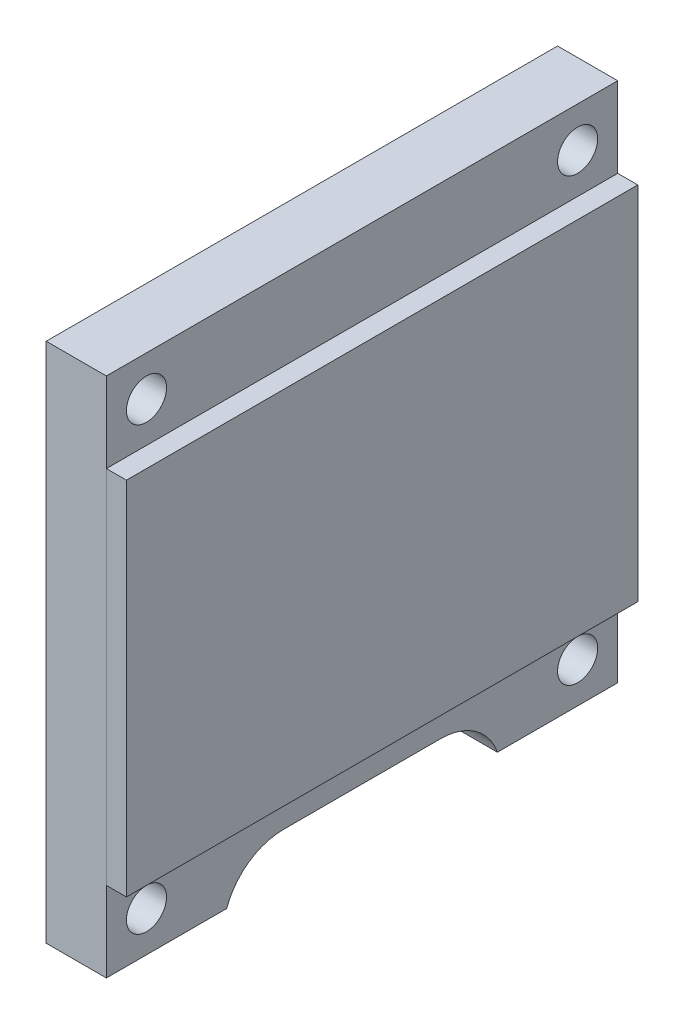
SolidWorks part; units mm, degrees
ref_plane "前视基准面" through (0, 0, 0) normal (0, 0, 1) x (1, 0, 0)
ref_plane "上视基准面" through (0, 0, 0) normal (0, 1, 0) x (1, 0, 0)
ref_plane "右视基准面" through (0, 0, 0) normal (1, 0, 0) x (0, 0, -1)
other "Configuration Table"
sketch "草图1" plane through (0, 0, 0) normal (1, 0, 0) x (0, 0, -1)
  line L0 (-12.75, -13) -> (-6.75, -13)
  line L2 (-12.75, -13) -> (-12.75, 13)
  line L3 (-12.75, 13) -> (12.75, 13)
  line L4 (12.75, -13) -> (12.75, 13)
  line L5 (-12.75, -13) -> (12.75, 13) construction
  line L6 (-12.75, 13) -> (12.75, -13) construction
  line L7 (-6.75, -13) -> (-6.75, -11)
  line L8 (-6.75, -11) -> (6.75, -11)
  line L9 (6.75, -11) -> (6.75, -13)
  line L10 (6.75, -13) -> (12.75, -13)
  circle A0 centre (-10.75, -11) radius 1
  circle A1 centre (-10.75, 11) radius 1
  circle A2 centre (10.75, 11) radius 1
  circle A3 centre (10.75, -11) radius 1
  point P0 (0, 0)
  point P18 (0, 0)
  point P20 (12.75, 11.1101)
  point P22 (11.0053, 13)
  dimension "D5" = 2
  dimension "D6" = 2
  dimension "D7" = 2
  dimension "D8" = 2
  dimension "D1" = 25.5
  dimension "D2" = 26
  dimension "D3" = 6
  dimension "D4" = 2
  dimension "D9" = 2
  dimension "D10" = 2
  dimension "D11" = 2
  dimension "D12" = 2
  dimension "D13" = 2
  dimension "D14" = 2
  dimension "D15" = 2
  dimension "D16" = 2
extrude "凸台-拉伸1" add sketch "草图1" along normal blind 3
fillet "圆角1" radius 3 2 edges at (1.5, -11, 6.75) (1.5, -11, -6.75)
sketch "草图2" plane through (3, 0, 0) normal (1, 0, 0) x (0, 0, -1)
  line L0 (12.75, -13) -> (12.75, 13) construction
  line L1 (-12.75, -9) -> (12.75, -9)
  line L2 (-12.75, -9) -> (-12.75, 9)
  line L3 (-12.75, 9) -> (12.75, 9)
  line L4 (12.75, -9) -> (12.75, 9)
  line L5 (-12.75, -9) -> (12.75, 9) construction
  line L6 (-12.75, 9) -> (12.75, -9) construction
  line L7 (12.75, 13) -> (-12.75, 13) construction
  point P0 (0, 0)
  dimension "D1" = 4
extrude "凸台-拉伸2" add sketch "草图2" along normal blind 1 separate body
